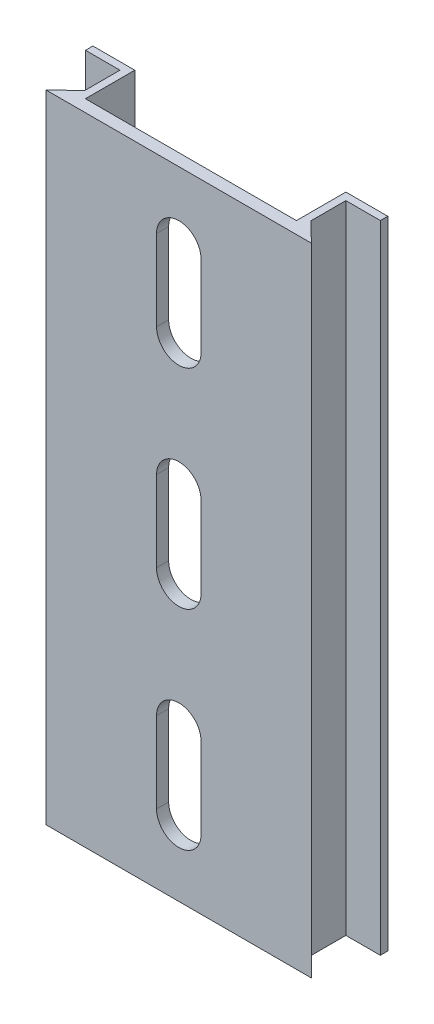
SolidWorks part; units mm, degrees
ref_plane "Front Plane" through (0, 0, 0) normal (0, 0, 1) x (1, 0, 0)
ref_plane "Top Plane" through (0, 0, 0) normal (0, 1, 0) x (1, 0, 0)
ref_plane "Right Plane" through (0, 0, 0) normal (1, 0, 0) x (0, 0, -1)
sketch "Sketch1" plane through (0, 0, 0) normal (0, 1, 0) x (1, 0, 0)
  line L0 (0, 0) -> (0, 1.4478)
  line L1 (-12.6365, 1.4478) -> (12.6365, 1.4478)
  line L2 (12.6365, 1.4478) -> (12.6365, 7.366)
  line L3 (12.6365, 7.366) -> (17.653, 7.366)
  line L4 (17.653, 7.366) -> (17.653, 6.477)
  line L5 (17.653, 6.477) -> (13.5255, 6.477)
  line L6 (13.5255, 6.477) -> (13.5255, 2.286)
  line L7 (13.5255, 2.286) -> (15.875, 0)
  line L8 (15.875, 0) -> (-15.875, 0)
  line L9 (-13.5255, 2.286) -> (-15.875, 0)
  line L10 (-13.5255, 6.477) -> (-13.5255, 2.286)
  line L11 (-17.653, 6.477) -> (-13.5255, 6.477)
  line L12 (-17.653, 7.366) -> (-17.653, 6.477)
  line L13 (-12.6365, 7.366) -> (-17.653, 7.366)
  line L14 (-12.6365, 1.4478) -> (-12.6365, 7.366)
  dimension "D1" = 15.875
  dimension "D2" = 13.5255
  dimension "D3" = 0.889
  dimension "D4" = 1.4478
  dimension "D5" = 7.366
  dimension "D6" = 0.889
  dimension "D7" = 2.286
  dimension "D8" = 17.653
extrude "Boss-Extrude1" add sketch "Sketch1" along normal mid plane 76.2 contours L1 L14 L13 L12 L11 L10 L9 L8 L0 | L8 L7 L6 L5 L4 L3 L2 L1 L0 region at (-7.9375, 0, -0.1913) region at (0.1913, 0, -0.7239)
sketch "Sketch2" plane through (0, 0, 0) normal (0, 0, 1) x (1, 0, 0)
  line L0 (0, -4.833) -> (0, 4.833) construction
  line L1 (-2.667, -4.833) -> (-2.667, 4.833)
  line L2 (2.667, -4.833) -> (2.667, 4.833)
  line L3 (-15.875, 0) -> (15.875, 0) construction
  line L4 (-15.875, 38.1) -> (-15.875, -38.1) construction
  line L5 (15.875, 38.1) -> (15.875, -38.1) construction
  arc A0 (-2.667, -4.833) -> (2.667, -4.833) centre (0, -4.833) ccw
  arc A1 (2.667, 4.833) -> (-2.667, 4.833) centre (0, 4.833) ccw
  point P3 (0, 0)
  point P15 (0, -7.5)
  point P16 (0, 7.5)
  dimension "D1" = 15
  dimension "D2" = 2.667
extrude "Cut-Extrude1" cut sketch "Sketch2" against normal through all
ref_plane "Plane1" through (0, 0, 0) normal (-1, 0, 0) x (0, 0, 1)
ref_plane "Plane2" through (0, 0, 0) normal (0, 1, 0) x (1, 0, 0)
pattern_linear "LPattern1" count 2 spacing 25 along (0, -1, 0) count 2 spacing 25 along (0, 1, 0) of "Cut-Extrude1"
